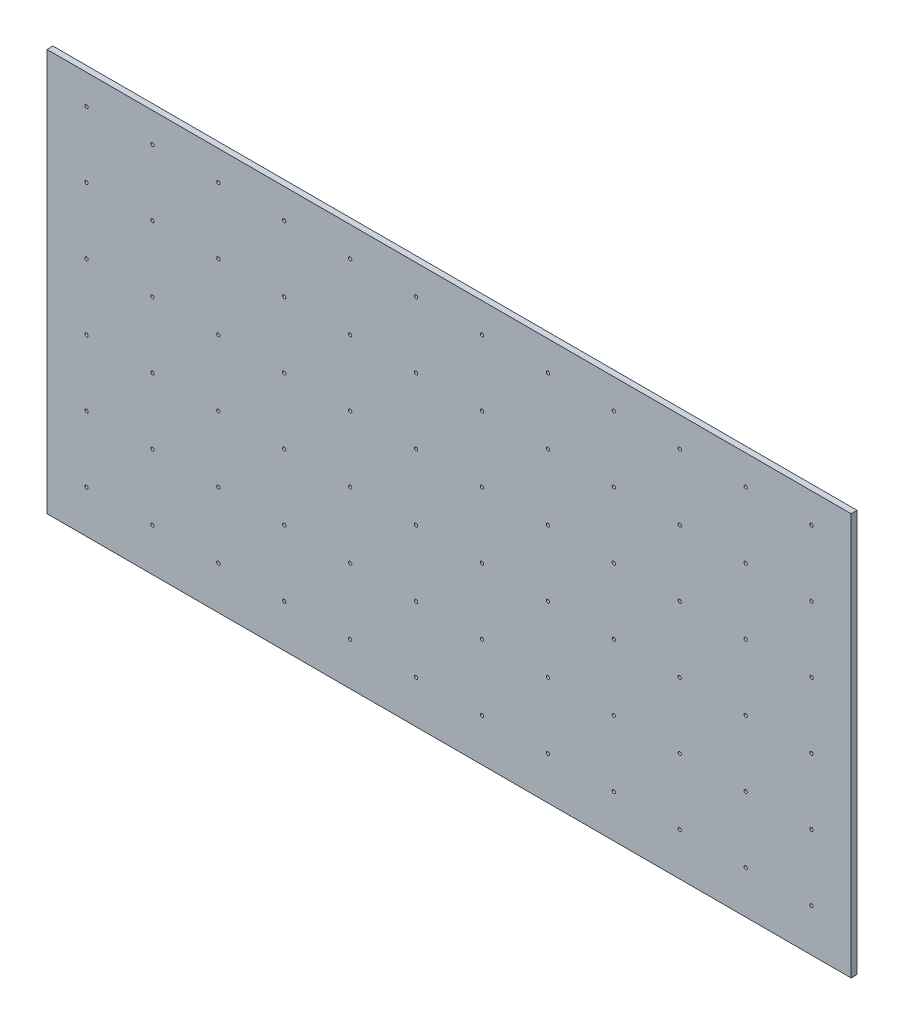
SolidWorks part; units mm, degrees
ref_plane "Front Plane" through (0, 0, 0) normal (0, 0, 1) x (1, 0, 0)
ref_plane "Top Plane" through (0, 0, 0) normal (0, 1, 0) x (1, 0, 0)
ref_plane "Right Plane" through (0, 0, 0) normal (1, 0, 0) x (0, 0, -1)
sketch "Sketch1" plane through (0, 0, 0) normal (0, 0, 1) x (1, 0, 0)
  line L1 (-2210.892, -618.5915) -> (229.108, -618.5915)
  line L2 (-2210.892, -618.5915) -> (-2210.892, 601.4085)
  line L3 (-2210.892, 601.4085) -> (229.108, 601.4085)
  line L4 (229.108, -618.5915) -> (229.108, 601.4085)
  circle A0 centre (-2090.892, 511.4085) radius 5
  circle A1 centre (-1890.892, 511.4085) radius 5
  circle A2 centre (-1690.892, 511.4085) radius 5
  circle A3 centre (-1490.892, 511.4085) radius 5
  circle A4 centre (-2090.892, 311.4085) radius 5
  circle A5 centre (-1890.892, 311.4085) radius 5
  circle A6 centre (-1690.892, 311.4085) radius 5
  circle A7 centre (-1490.892, 311.4085) radius 5
  circle A8 centre (-1290.892, 511.4085) radius 5
  circle A9 centre (-1290.892, 311.4085) radius 5
  circle A10 centre (-1090.892, 511.4085) radius 5
  circle A11 centre (-1090.892, 311.4085) radius 5
  circle A12 centre (-890.892, 511.4085) radius 5
  circle A13 centre (-890.892, 311.4085) radius 5
  circle A14 centre (-890.892, 111.4085) radius 5
  circle A15 centre (-1090.892, 111.4085) radius 5
  circle A16 centre (-1290.892, 111.4085) radius 5
  circle A17 centre (-1490.892, 111.4085) radius 5
  circle A18 centre (-1690.892, 111.4085) radius 5
  circle A19 centre (-1890.892, 111.4085) radius 5
  circle A20 centre (-2090.892, 111.4085) radius 5
  circle A21 centre (-2090.892, -88.5915) radius 5
  circle A22 centre (-1890.892, -88.5915) radius 5
  circle A23 centre (-1690.892, -88.5915) radius 5
  circle A24 centre (-1490.892, -88.5915) radius 5
  circle A25 centre (-1290.892, -88.5915) radius 5
  circle A26 centre (-1090.892, -88.5915) radius 5
  circle A27 centre (-890.892, -88.5915) radius 5
  circle A28 centre (-690.892, -88.5915) radius 5
  circle A29 centre (-490.892, -88.5915) radius 5
  circle A30 centre (-490.892, 111.4085) radius 5
  circle A31 centre (-490.892, 311.4085) radius 5
  circle A32 centre (-490.892, 511.4085) radius 5
  circle A33 centre (-690.892, 511.4085) radius 5
  circle A34 centre (-690.892, 311.4085) radius 5
  circle A35 centre (-690.892, 111.4085) radius 5
  circle A36 centre (-490.892, -288.5915) radius 5
  circle A37 centre (-690.892, -288.5915) radius 5
  circle A38 centre (-890.892, -288.5915) radius 5
  circle A39 centre (-1090.892, -288.5915) radius 5
  circle A40 centre (-1290.892, -288.5915) radius 5
  circle A41 centre (-1490.892, -288.5915) radius 5
  circle A42 centre (-1690.892, -288.5915) radius 5
  circle A43 centre (-1890.892, -288.5915) radius 5
  circle A44 centre (-2090.892, -288.5915) radius 5
  circle A45 centre (-2090.892, -488.5915) radius 5
  circle A46 centre (-1890.892, -488.5915) radius 5
  circle A47 centre (-1690.892, -488.5915) radius 5
  circle A48 centre (-1490.892, -488.5915) radius 5
  circle A49 centre (-1290.892, -488.5915) radius 5
  circle A50 centre (-1090.892, -488.5915) radius 5
  circle A51 centre (-890.892, -488.5915) radius 5
  circle A52 centre (-690.892, -488.5915) radius 5
  circle A53 centre (-490.892, -488.5915) radius 5
  circle A54 centre (-290.892, 511.4085) radius 5
  circle A55 centre (-290.892, 311.4085) radius 5
  circle A56 centre (-290.892, 111.4085) radius 5
  circle A57 centre (-290.892, -88.5915) radius 5
  circle A58 centre (-290.892, -288.5915) radius 5
  circle A59 centre (-290.892, -488.5915) radius 5
  circle A60 centre (-90.892, 511.4085) radius 5
  circle A61 centre (-90.892, 311.4085) radius 5
  circle A62 centre (-90.892, 111.4085) radius 5
  circle A63 centre (-90.892, -88.5915) radius 5
  circle A64 centre (-90.892, -288.5915) radius 5
  circle A65 centre (-90.892, -488.5915) radius 5
  circle A66 centre (109.108, -488.5915) radius 5
  circle A67 centre (109.108, -288.5915) radius 5
  circle A68 centre (109.108, -88.5915) radius 5
  circle A69 centre (109.108, 111.4085) radius 5
  circle A70 centre (109.108, 311.4085) radius 5
  circle A71 centre (109.108, 511.4085) radius 5
  point P40 (-2090.892, 511.4085)
  point P41 (-1890.892, 511.4085)
  point P42 (-1690.892, 511.4085)
  point P43 (-1490.892, 511.4085)
  point P44 (-1290.892, 511.4085)
  point P45 (-1090.892, 511.4085)
  point P46 (-2090.892, 311.4085)
  point P47 (-1890.892, 311.4085)
  point P48 (-1690.892, 311.4085)
  point P49 (-1490.892, 311.4085)
  point P50 (-1290.892, 311.4085)
  point P51 (-1090.892, 311.4085)
  point P52 (-1090.892, 111.4085)
  point P53 (-1290.892, 111.4085)
  point P54 (-1490.892, 111.4085)
  point P55 (-1690.892, 111.4085)
  point P56 (-1890.892, 111.4085)
  point P57 (-2090.892, 111.4085)
  point P58 (-890.892, 311.4085)
  point P59 (-890.892, 111.4085)
  point P60 (-890.892, 511.4085)
  point P61 (-690.892, 511.4085)
  point P62 (-490.892, 511.4085)
  point P63 (-290.892, 511.4085)
  point P64 (-90.892, 511.4085)
  point P65 (109.108, 511.4085)
  point P66 (109.108, 311.4085)
  point P67 (-90.892, 311.4085)
  point P68 (-290.892, 311.4085)
  point P69 (-490.892, 311.4085)
  point P70 (-690.892, 311.4085)
  point P71 (-690.892, 111.4085)
  point P72 (-490.892, 111.4085)
  point P73 (-290.892, 111.4085)
  point P74 (-90.892, 111.4085)
  point P75 (109.108, 111.4085)
  point P76 (109.108, -88.5915)
  point P77 (-90.892, -88.5915)
  point P78 (-290.892, -88.5915)
  point P79 (-490.892, -88.5915)
  point P80 (-690.892, -88.5915)
  point P81 (-890.892, -88.5915)
  point P82 (-890.892, -288.5915)
  point P83 (-690.892, -288.5915)
  point P84 (-490.892, -288.5915)
  point P85 (-290.892, -288.5915)
  point P86 (-90.892, -288.5915)
  point P87 (109.108, -288.5915)
  point P88 (109.108, -488.5915)
  point P89 (-90.892, -488.5915)
  point P90 (-290.892, -488.5915)
  point P91 (-490.892, -488.5915)
  point P92 (-690.892, -488.5915)
  point P93 (-890.892, -488.5915)
  point P94 (-1090.892, -488.5915)
  point P95 (-1090.892, -288.5915)
  point P96 (-1090.892, -88.5915)
  point P97 (-1290.892, -88.5915)
  point P98 (-1290.892, -288.5915)
  point P99 (-1290.892, -488.5915)
  point P100 (-1490.892, -488.5915)
  point P101 (-1490.892, -288.5915)
  point P102 (-1490.892, -88.5915)
  point P103 (-1690.892, -488.5915)
  point P104 (-1690.892, -288.5915)
  point P105 (-1890.892, -488.5915)
  point P106 (-1890.892, -288.5915)
  point P107 (-1690.892, -88.5915)
  point P108 (-1890.892, -88.5915)
  point P109 (-2090.892, -88.5915)
  point P110 (-2090.892, -288.5915)
  point P111 (-2090.892, -488.5915)
  dimension "D1" = 2440
  dimension "D2" = 1220
extrude "Boss-Extrude1" add sketch "Sketch1" along normal blind 18
